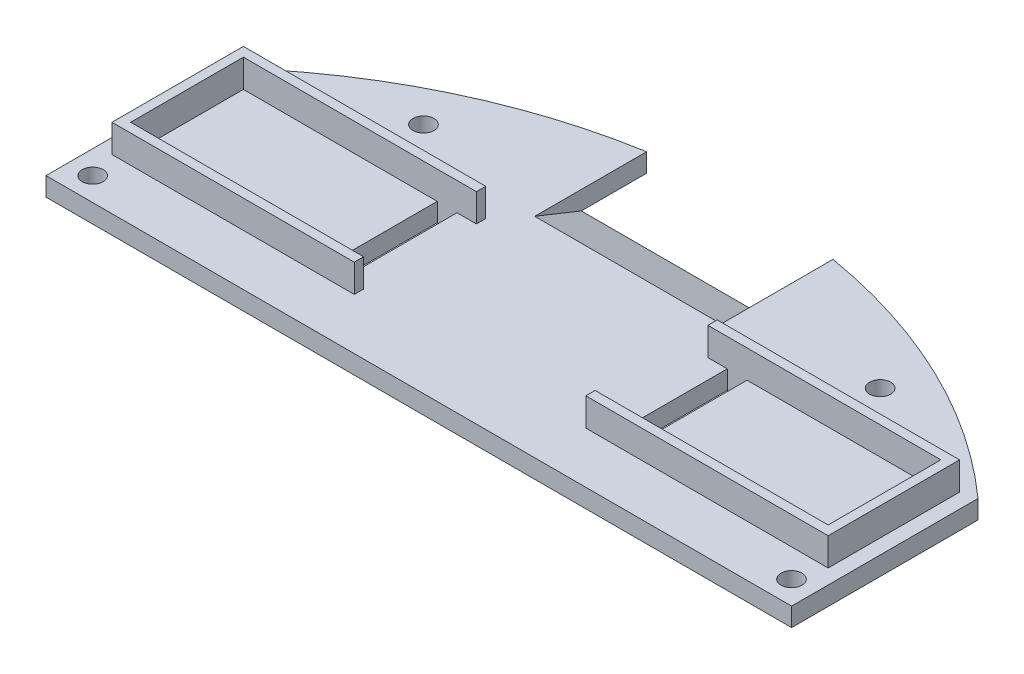
SolidWorks part; units mm, degrees
ref_plane "Front Plane" through (0, 0, 0) normal (0, 0, 1) x (1, 0, 0)
ref_plane "Top Plane" through (0, 0, 0) normal (0, 1, 0) x (1, 0, 0)
ref_plane "Right Plane" through (0, 0, 0) normal (1, 0, 0) x (0, 0, -1)
sketch "Sketch2" plane through (0, 0, 0) normal (0, 1, 0) x (1, 0, 0)
  line L0 (-10, 24.4394) -> (-10, 17.4394)
  line L1 (-40, -10) -> (40, -10)
  line L2 (-40, -10) -> (-40, 10)
  line L4 (40, -10) -> (40, 10)
  line L5 (-40, -10) -> (40, 10) construction
  line L6 (-40, 10) -> (40, -10) construction
  line L7 (0, -55) -> (0, 55) construction
  line L8 (-10, 17.4394) -> (10, 17.4394)
  line L13 (14.5, 8.6) -> (16.62, 8.6)
  line L14 (14.5, 8.6) -> (14.5, -3.5)
  line L15 (14.5, -3.5) -> (16.62, -3.5)
  line L16 (16.62, 8.6) -> (16.62, -3.5)
  line L21 (10, 17.4394) -> (10, 24.4394)
  line L22 (0, 17.4394) -> (0, -10) construction
  line L23 (-14.5, -3.5) -> (-16.62, -3.5)
  line L24 (-16.62, 8.6) -> (-16.62, -3.5)
  line L25 (-14.5, 8.6) -> (-16.62, 8.6)
  line L26 (-14.5, 8.6) -> (-14.5, -3.5)
  arc A0 (-40, 10) -> (-10, 24.4394) centre (0, -34.7214) cw
  arc A1 (10, 24.4394) -> (40, 10) centre (0, -34.7214) cw
  circle A3 centre (-37.4904, -7.5) radius 1.125
  circle A6 centre (37.4904, -7.5) radius 1.125
  circle A8 centre (-24.5, 15) radius 1.125
  circle A9 centre (24.5, 15) radius 1.125
  point P0 (0, 0)
  point P9 (0, -10)
  point P30 (0, 17.4394)
  dimension "D3" = 60
  dimension "D7" = 2.25
  dimension "D1" = 80
  dimension "D2" = 20
  dimension "D5" = 37.4904
  dimension "D6" = 7.5
  dimension "D8" = 15
  dimension "D9" = 24.5
  dimension "D10" = 20
  dimension "D11" = 7
  dimension "D12" = 2.12
  dimension "D13" = 12.1
  dimension "D14" = 4
  dimension "D15" = 14.5
extrude "Boss-Extrude2" add sketch "Sketch2" along normal blind 2
sketch "Sketch3" plane through (0, 2, 0) normal (0, 1, 0) x (1, 0, 0)
  line L0 (16.62, -3.5) -> (16.62, 8.6) construction
  line L1 (12.42, -3.5) -> (37.42, -3.5)
  line L2 (12.42, -3.5) -> (12.42, -4.5)
  line L3 (12.42, -4.5) -> (38.42, -4.5)
  line L6 (38.42, -4.5) -> (38.42, 9.6)
  line L8 (37.42, -3.5) -> (37.42, 8.6)
  line L9 (37.42, 8.6) -> (12.42, 8.6)
  line L11 (38.42, 9.6) -> (12.42, 9.6)
  line L12 (12.42, 8.6) -> (12.42, 9.6)
  line L13 (16.62, 8.6) -> (14.5, 8.6) construction
  line L14 (14.5, -3.5) -> (16.62, -3.5) construction
  line L15 (0, 0) -> (0, 17.4394) construction
  line L17 (10, 17.4394) -> (-10, 17.4394) construction
  line L18 (-12.42, -3.5) -> (-12.42, -4.5)
  line L19 (-12.42, -3.5) -> (-37.42, -3.5)
  line L20 (-37.42, -3.5) -> (-37.42, 8.6)
  line L21 (-37.42, 8.6) -> (-12.42, 8.6)
  line L22 (-12.42, 8.6) -> (-12.42, 9.6)
  line L23 (-38.42, 9.6) -> (-12.42, 9.6)
  line L24 (-38.42, -4.5) -> (-38.42, 9.6)
  line L25 (-12.42, -4.5) -> (-38.42, -4.5)
  dimension "D1" = 1
  dimension "D2" = 1
  dimension "D3" = 20.8
  dimension "D4" = 26
extrude "Boss-Extrude3" add sketch "Sketch3" along normal blind 3
chamfer "Chamfer1" distance 2 distance2 5 1 edges at (0, 2, -17.4394) first distance on face at (0, 1, -17.4394)
